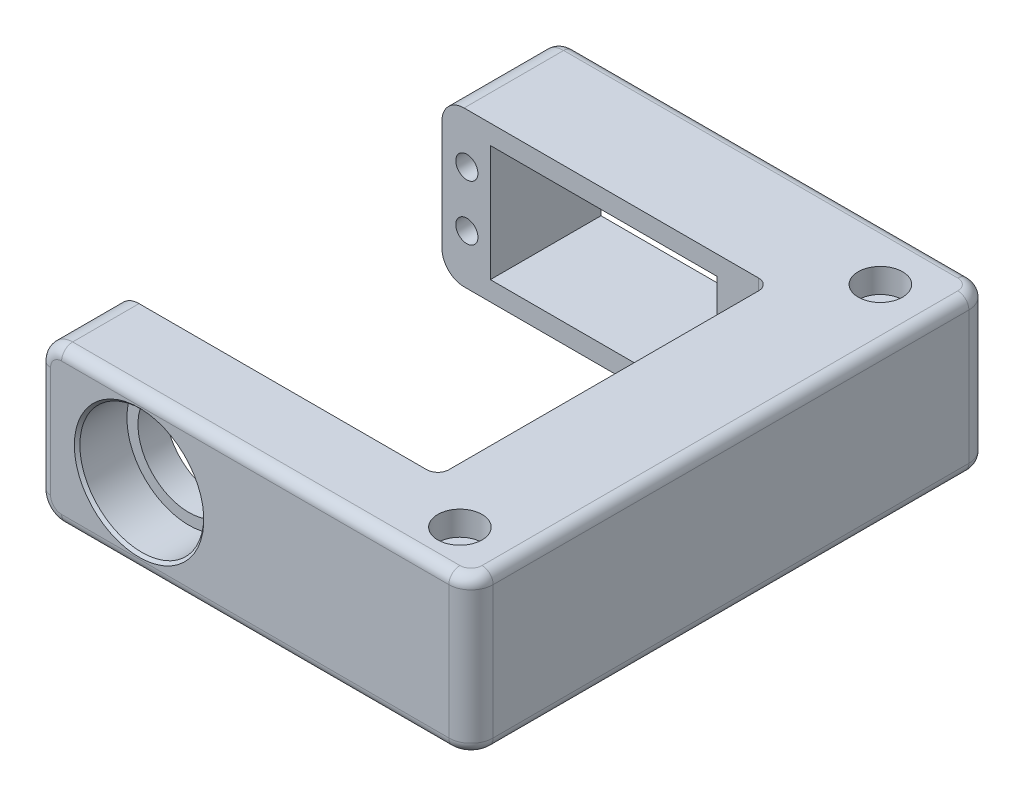
SolidWorks part; units mm, degrees
ref_plane "Top Plane" through (0, 0, 0) normal (0, 0, 1) x (1, 0, 0)
ref_plane "Right Plane" through (0, 0, 0) normal (0, 1, 0) x (1, 0, 0)
ref_plane "Front Plane" through (0, 0, 0) normal (1, 0, 0) x (0, 0, -1)
sketch "Sketch1" plane through (0, 0, 0) normal (0, 0, 1) x (1, 0, 0)
  line L0 (-10, 0) -> (30, 0) construction
  line L1 (-10, 10) -> (30, 10) construction
  line L2 (-10, 10) -> (-10, -10) construction
  line L3 (-10, -10) -> (30, -10) construction
  line L4 (30, 10) -> (30, -10) construction
  line L5 (-10, 10) -> (-17.25, 10) construction
  line L6 (-17.25, 10) -> (-17.25, -10) construction
  line L7 (-17.25, -10) -> (-10, -10) construction
  line L8 (10, 10) -> (10, -10) construction
  line L9 (37.25, -10) -> (30, -10) construction
  line L10 (37.25, 10) -> (37.25, -10) construction
  line L11 (30, 10) -> (37.25, 10) construction
  line L12 (40, 14) -> (40, -14) construction
  line L13 (-19.25, 14) -> (60, 14)
  line L14 (-19.25, 14) -> (-19.25, -14)
  line L15 (-19.25, -14) -> (60, -14)
  line L16 (60, 14) -> (60, -14)
  circle A0 centre (0, 0) radius 11 construction
  circle A1 centre (0, 0) radius 4 construction
  circle A2 centre (-14.75, 5) radius 2 construction
  circle A3 centre (-14.75, -5) radius 2 construction
  circle A4 centre (34.75, -5) radius 2 construction
  circle A5 centre (34.75, 5) radius 2 construction
  dimension "D1" = 22
  dimension "D2" = 8
  dimension "D12" = 4
  dimension "D3" = 40
  dimension "D4" = 20
  dimension "D5" = 54.5
  dimension "D6" = 37.25
  dimension "D7" = 20
  dimension "D8" = 40
  dimension "D9" = 14
  dimension "D10" = 14
  dimension "D11" = 2
  dimension "D13" = 10
  dimension "D14" = 49.5
extrude "Boss-Extrude1" add sketch "Sketch1" along normal blind 20
sketch "Sketch2" plane through (0, 0, 20) normal (0, 0, 1) x (1, 0, 0)
  line L1 (40, 14) -> (60, 14)
  line L2 (40, 14) -> (40, -14)
  line L3 (40, -14) -> (60, -14)
  line L4 (60, 14) -> (60, -14)
extrude "Boss-Extrude2" add sketch "Sketch2" along normal blind 60
sketch "Sketch3" plane through (0, 0, 80) normal (0, 0, 1) x (1, 0, 0)
  line L0 (-19.25, -14) -> (60, -14) construction
  line L1 (60, 14) -> (-18, 14)
  line L2 (60, 14) -> (60, -14)
  line L3 (60, -14) -> (-18, -14)
  line L4 (-18, 14) -> (-18, -14)
  dimension "D1" = 18
extrude "Boss-Extrude3" add sketch "Sketch3" along normal blind 14
sketch "Sketch4" plane through (0, 0, 20) normal (0, 0, 1) x (1, 0, 0)
  line L8 (-10.5, -10.5) -> (30.5, -10.5)
  line L9 (30.5, -10.5) -> (30.5, 10.5)
  line L10 (30.5, 10.5) -> (-10.5, 10.5)
  line L11 (-10.5, 10.5) -> (-10.5, -10.5)
  line L12 (-10.5, -10.5) -> (30.5, -10.5)
  line L13 (30.5, -10.5) -> (30.5, 10.5)
  line L14 (30.5, 10.5) -> (-10.5, 10.5)
  line L15 (-10.5, 10.5) -> (-10.5, -10.5)
  dimension "D1" = 0.5
extrude "Cut-Extrude1" cut sketch "Sketch4" against normal through all
sketch "Sketch5" plane through (0, 0, 20) normal (0, 0, 1) x (1, 0, 0)
  circle A0 centre (34.75, -5) radius 2 construction
  circle A1 centre (34.75, 5) radius 2 construction
  circle A2 centre (-14.75, -5) radius 2 construction
  circle A3 centre (-14.75, 5) radius 2 construction
  circle A4 centre (34.75, -5) radius 2
  circle A5 centre (34.75, 5) radius 2
  circle A6 centre (-14.75, -5) radius 2
  circle A7 centre (-14.75, 5) radius 2
extrude "Cut-Extrude2" cut sketch "Sketch5" against normal through all
sketch "Sketch6" plane through (0, 0, 0) normal (0, 0, -1) x (-1, 0, 0)
  line L0 (-10, 10.5) -> (-10, -10.5) construction
  line L1 (-34.75, 8.4641) -> (-37.75, 6.7321)
  line L2 (-37.75, 6.7321) -> (-37.75, 3.2679)
  line L3 (-37.75, 3.2679) -> (-34.75, 1.5359)
  line L4 (-34.75, 1.5359) -> (-31.75, 3.2679)
  line L5 (-31.75, 3.2679) -> (-31.75, 6.7321)
  line L6 (-31.75, 6.7321) -> (-34.75, 8.4641)
  line L7 (-34.75, -1.5359) -> (-37.75, -3.2679)
  line L8 (-37.75, -3.2679) -> (-37.75, -6.7321)
  line L9 (-37.75, -6.7321) -> (-34.75, -8.4641)
  line L10 (-34.75, -8.4641) -> (-31.75, -6.7321)
  line L11 (-31.75, -6.7321) -> (-31.75, -3.2679)
  line L12 (-31.75, -3.2679) -> (-34.75, -1.5359)
  line L13 (-30.5, 10.5) -> (10.5, 10.5) construction
  line L14 (10.5, -10.5) -> (-30.5, -10.5) construction
  line L15 (11.75, -3.2679) -> (14.75, -1.5359)
  line L16 (11.75, -6.7321) -> (11.75, -3.2679)
  line L17 (14.75, -8.4641) -> (11.75, -6.7321)
  line L18 (17.75, -6.7321) -> (14.75, -8.4641)
  line L19 (17.75, -3.2679) -> (17.75, -6.7321)
  line L20 (14.75, -1.5359) -> (17.75, -3.2679)
  line L21 (11.75, 6.7321) -> (14.75, 8.4641)
  line L22 (11.75, 3.2679) -> (11.75, 6.7321)
  line L23 (14.75, 1.5359) -> (11.75, 3.2679)
  line L24 (17.75, 3.2679) -> (14.75, 1.5359)
  line L25 (17.75, 6.7321) -> (17.75, 3.2679)
  line L26 (14.75, 8.4641) -> (17.75, 6.7321)
  circle A0 centre (-34.75, 5) radius 3 construction
  circle A1 centre (-34.75, -5) radius 3 construction
  circle A2 centre (14.75, -5) radius 3 construction
  circle A3 centre (14.75, 5) radius 3 construction
  dimension "D1" = 6
extrude "Cut-Extrude3" cut sketch "Sketch6" against normal offset from surface (14 mm away) 6 up to face at (36.75, 5, 20)
sketch "Sketch7" plane through (0, 0, 94) normal (0, 0, 1) x (1, 0, 0)
  circle A2 centre (0, 0) radius 11.2
  circle A3 centre (0, 0) radius 11.2
  dimension "D1" = 0.2
extrude "Cut-Extrude4" cut sketch "Sketch7" against normal blind 9
sketch "Sketch8" plane through (0, 0, 85) normal (0, 0, 1) x (1, 0, 0)
  circle A0 centre (0, 0) radius 9.2
  circle A1 centre (0, 0) radius 11.2 construction
  dimension "D1" = 2
extrude "Cut-Extrude5" cut sketch "Sketch8" against normal up to next
fillet "Fillet1" radius 4 4 edges at (-18, -14, 87) (-18, 14, 87) (-19.25, -14, 10) (-19.25, 14, 10)
sketch "Sketch12" plane through (0, 14, 0) normal (0, 1, 0) x (1, 0, 0)
  line L0 (60, 0) -> (-15.25, 0) construction
  line L1 (60, -94) -> (60, 0) construction
  line L2 (60, -94) -> (-14, -94) construction
  circle A0 centre (50, -10) radius 2 construction
  circle A1 centre (50, -10) radius 3.75 construction
  circle A2 centre (50, -86) radius 2 construction
  circle A3 centre (50, -86) radius 3.75 construction
  dimension "D1" = 4
  dimension "D2" = 7.5
  dimension "D5" = 8
  dimension "D3" = 10
  dimension "D4" = 10
  dimension "D6" = 10
hole_wizard "CBORE for M4 Hex Socket Head Cap Screw1" positions "Sketch13" profile "Sketch14" counterbore size "M4" standard "ISO" end condition through all
sketch "Sketch13" plane through (0, 14, 0) normal (0, 1, 0) x (1, 0, 0)
  point P2 (50, -10)
  point P7 (50, -86)
sketch "Sketch14" plane through (50, 14, 10) normal (1, 0, 0) x (0, 0, 1)
  line L0 (0, 0) -> (0, 28)
  line L1 (0, 28) -> (2.15, 28)
  line L3 (2.15, 28) -> (2.15, 4.4)
  line L4 (2.15, 4.4) -> (4, 4.4)
  line L5 (4, 4.4) -> (4, 0)
  line L7 (4, 0) -> (0, 0)
  line L11 (0, -6.35) -> (0, 107.95) construction
  dimension "Thru Hole Dia." = 4.3
  dimension "Thru Hole Depth" = 28
  dimension "C'Bore Dia." = 8
  dimension "C'Bore Depth" = 4.4
fillet "Fillet3" radius 4 2 edges at (60, 0, 0) (60, 0, 94)
fillet "Fillet4" radius 2 2 edges at (40, 0, 20) (40, 0, 80)
fillet "Fillet5" radius 2 16 edges at (58.8284, -14, 92.8284) (21, -14, 94) (-16.8284, -12.8284, 94) (-18, 0, 94) (-16.8284, 12.8284, 94) (21, 14, 94) (58.8284, 14, 92.8284) (60, 14, 47) (58.8284, 14, 1.1716) (20.375, 14, 0) (-18.0784, 12.8284, 0) (-19.25, 0, 0) (-18.0784, -12.8284, 0) (20.375, -14, 0) (58.8284, -14, 1.1716) (60, -14, 47)
chamfer "Chamfer1" distance 0.5 angle 45 1 edges at (11.2, 0, 94)
